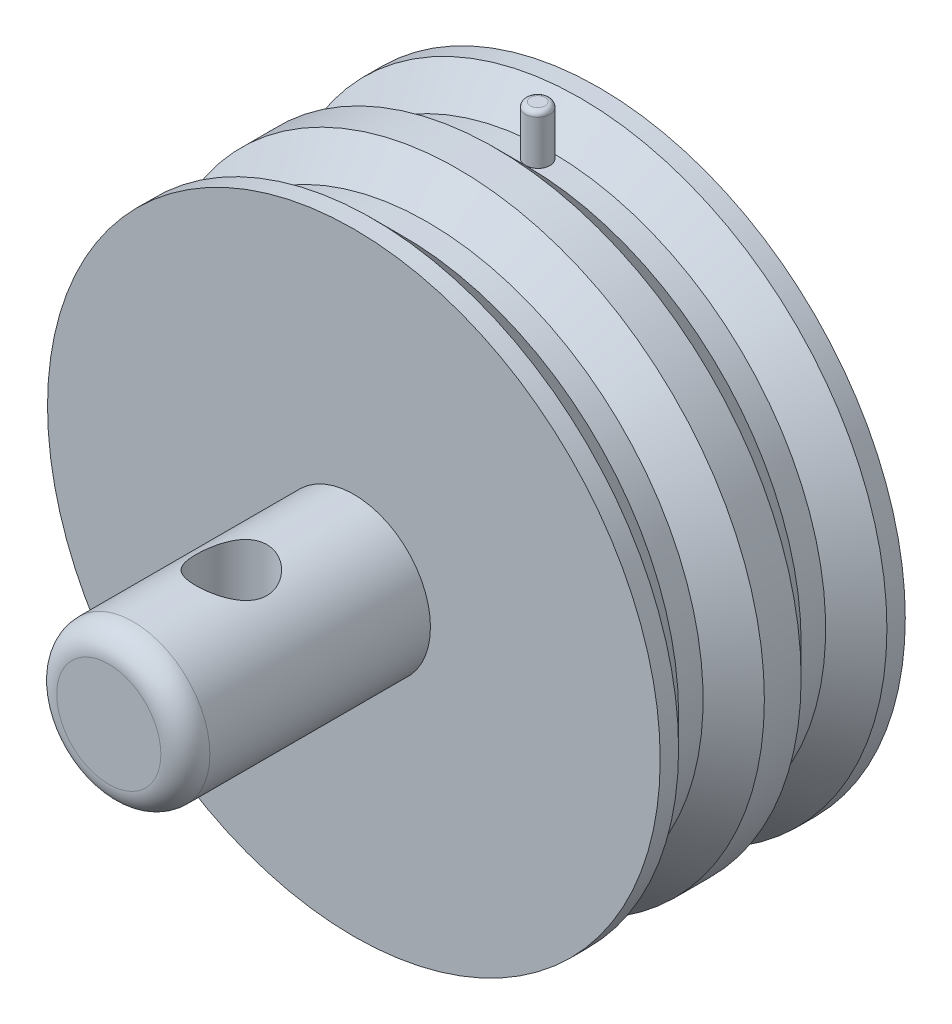
SolidWorks part; units mm, degrees
ref_plane "Plan de face" through (0, 0, 0) normal (0, 0, 1) x (1, 0, 0)
ref_plane "Plan de dessus" through (0, 0, 0) normal (0, 1, 0) x (1, 0, 0)
ref_plane "Plan de droite" through (0, 0, 0) normal (1, 0, 0) x (0, 0, -1)
sketch "Esquisse1" plane through (0, 0, 0) normal (0, 0, 1) x (1, 0, 0)
  circle A0 centre (0, 0) radius 3.125
  dimension "D1" = 6.25
extrude "Boss.-Extru.1" add sketch "Esquisse1" along normal blind 10
fillet "Congé1" radius 1 1 edges at (3.125, 0, 10)
sketch "Esquisse2" plane through (0, 0, 0) normal (0, 0, -1) x (-1, 0, 0)
  circle A0 centre (0, 0) radius 12.5
  dimension "D1" = 25
extrude "Boss.-Extru.3" add sketch "Esquisse2" along normal blind 10
sketch "Esquisse5" plane through (0, 0, 0) normal (1, 0, 0) x (0, 0, -1)
  line L0 (0.75, 12.5) -> (2, 11.25)
  line L1 (10, 12.5) -> (0, 12.5) construction
  line L2 (2, 11.25) -> (3, 11.25)
  line L3 (3, 11.25) -> (4.25, 12.5)
  line L4 (4.25, 12.5) -> (0.75, 12.5)
  line L5 (0, 0) -> (10, 0) construction
  line L6 (10, -12.5) -> (10, 12.5) construction
  line L7 (5, 0) -> (5, 12.5) construction
  line L8 (0, 12.5) -> (0.75, 12.5) construction
  line L9 (4.25, 12.5) -> (5, 12.5) construction
  line L10 (5.75, 12.5) -> (9.25, 12.5)
  line L11 (7, 11.25) -> (5.75, 12.5)
  line L12 (9.25, 12.5) -> (8, 11.25)
  line L13 (8, 11.25) -> (7, 11.25)
  point P14 (0.5691, 7.499)
  point P20 (2.8126, 10.4634)
  dimension "D1" = 45
  dimension "D2" = 1
  dimension "D3" = 3.5
revolve "Enlèvement de matière-Révolution1" cut sketch "Esquisse5" angle 360 about L5
sketch "Esquisse6" plane through (0, 0, 0) normal (0, 1, 0) x (1, 0, 0)
  line L0 (0, 0) -> (0, -10) construction
  line L1 (-2.125, -10) -> (2.125, -10) construction
  circle A0 centre (0, -5) radius 1.45
  point P7 (0, -5)
  dimension "D1" = 2.9
extrude "Enlèv. mat.-Extru.1" cut sketch "Esquisse6" against normal through all both and the other way through all
ref_plane "Plan1" through (0, 11.25, 0) normal (0, 1, 0) x (1, 0, 0)
sketch "Esquisse7" plane through (0, 11.25, 0) normal (0, 1, 0) x (1, 0, 0)
  line L0 (0, 7.5) -> (0, 0) construction
  line L1 (-1.2647, 7) -> (-1.2647, 8) construction
  line L2 (11.25, 7) -> (-11.25, 7) construction
  line L3 (11.25, 8) -> (-11.25, 8) construction
  circle A0 centre (0, 7.5) radius 0.5
  point P10 (-1.2647, 7.5)
  dimension "D1" = 1
extrude "Boss.-Extru.4" add sketch "Esquisse7" along normal blind 2 and the other way blind 1
ref_plane "Plan2" through (0, -11.25, 0) normal (0, -1, 0) x (-1, 0, 0)
sketch "Esquisse8" plane through (0, -11.25, 0) normal (0, -1, 0) x (-1, 0, 0)
  line L0 (0, 0) -> (0, 2.5) construction
  line L1 (3.0489, 3) -> (3.0489, 2) construction
  line L2 (-11.25, 3) -> (11.25, 3) construction
  line L3 (-11.25, 2) -> (11.25, 2) construction
  circle A0 centre (0, 2.5) radius 0.5
  point P10 (3.0489, 2.5)
  dimension "D1" = 1
extrude "Boss.-Extru.5" add sketch "Esquisse8" along normal blind 2 and the other way blind 1
fillet "Congé2" radius 0.2 2 edges at (0, 13.25, -7) (0, -13.25, -3)
